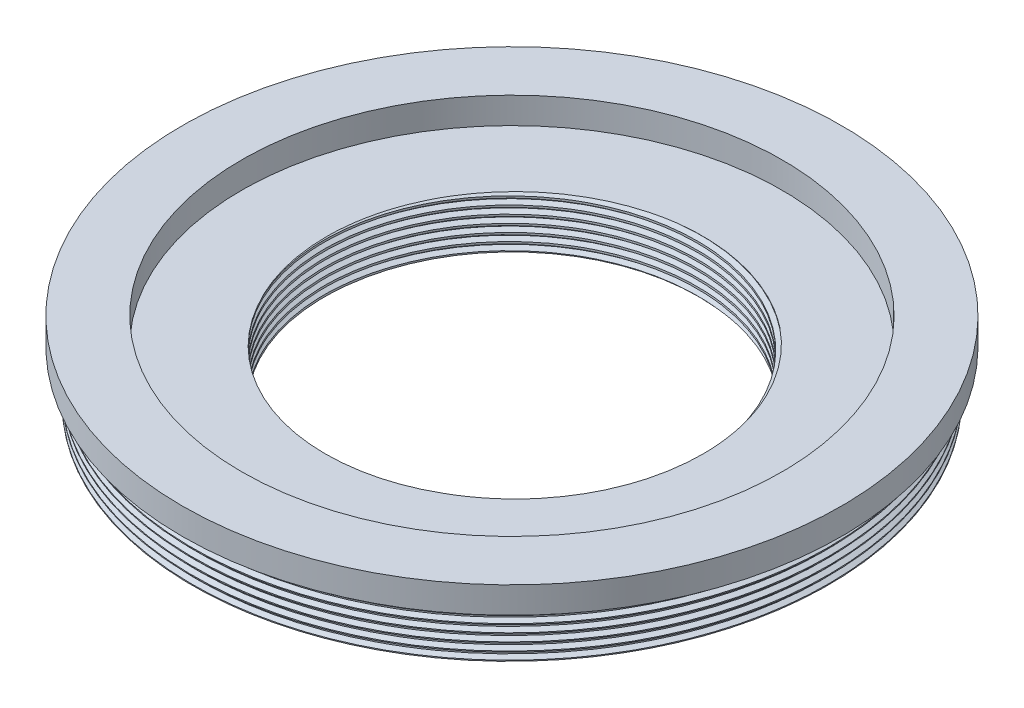
SolidWorks part; units mm, degrees
ref_plane "Front Plane" through (0, 0, 0) normal (0, 0, 1) x (1, 0, 0)
ref_plane "Top Plane" through (0, 0, 0) normal (0, 1, 0) x (1, 0, 0)
ref_plane "Right Plane" through (0, 0, 0) normal (1, 0, 0) x (0, 0, -1)
sketch "Sketch1" plane through (0, 0, 0) normal (0, 1, 0) x (1, 0, 0)
  circle A0 centre (0, 0) radius 23.8
  dimension "D1" = 47.6
extrude "Boss-Extrude1" add sketch "Sketch1" along normal blind 12.7
thread "MinColWidth_OnTracking1" pitch 0.6 method extrude profile "HeaderRowsCount1" start angle 0, offset 0, length 12.7, pitch 0.6, diameter 47.6
ref_plane "Plane1" through (-23.8, 12.7, 0) normal (0, 0, 1) x (-1, 0, 0)
sketch "HeaderRowsCount1" plane through (-23.8, 12.7, 0) normal (0, 0, 1) x (-1, 0, 0)
  line L0 (0, 0) -> (0, 0.6) construction
  line L1 (0, 0) -> (0.3248, 0.1875)
  line L2 (0.3248, 0.1875) -> (0.3248, 0.2625)
  line L3 (0.3248, 0.2625) -> (0, 0.45)
  line L4 (0.3248, 0.225) -> (0, 0.225) construction
  line L11 (0, 0) -> (0, 0.45)
  point P2 (0, 0)
  dimension "Pitch" = 0.6
  dimension "Profile_Angle" = 60
  dimension "Profile_Land" = 0.075
  dimension "Profile_Height" = 0.3248
sketch "Sketch2" plane through (0, 0, 0) normal (0, 0, 1) x (1, 0, 0)
  line L0 (0, 0) -> (0, 19.0669) construction
  line L1 (-25, 7.905) -> (25, 7.905)
  line L2 (-25, 7.905) -> (-25, 4.095)
  line L3 (-25, 4.095) -> (25, 4.095)
  line L4 (25, 7.905) -> (25, 4.095)
  line L5 (-25, 7.905) -> (25, 4.095) construction
  line L6 (-25, 4.095) -> (25, 7.905) construction
  point P0 (0, 6)
  dimension "D1" = 50
  dimension "D2" = 3.81
  dimension "D3" = 6
extrude "Cut-Extrude2" cut sketch "Sketch2" against normal through all both and the other way through all flip side to cut
sketch "Sketch3" plane through (0, 7.905, 0) normal (0, 1, 0) x (1, 0, 0)
  circle A0 centre (0, 0) radius 25
  dimension "D1" = 50
extrude "Boss-Extrude2" add sketch "Sketch3" along normal blind 2
sketch "Sketch4" plane through (0, 9.905, 0) normal (0, 1, 0) x (1, 0, 0)
  circle A0 centre (0, 0) radius 20.5
  dimension "D1" = 41
extrude "Cut-Extrude3" cut sketch "Sketch4" against normal up to surface (2 mm away) up to face at (0, 7.905, 25)
sketch "Sketch5" plane through (0, 7.905, 0) normal (0, 1, 0) x (1, 0, 0)
  circle A0 centre (0, 0) radius 14.15
  dimension "D1" = 28.3
extrude "Cut-Extrude4" cut sketch "Sketch5" against normal through all
thread "Thread1" pitch 0.6 method cut profile "Thread Profile1" start angle 0, offset 4, length 10, pitch 0.6, diameter 28.3
ref_plane "Plane2" through (-14.15, 11.905, 0) normal (0, 0, 1) x (-1, 0, 0)
sketch "Thread Profile1" plane through (-14.15, 11.905, 0) normal (0, 0, 1) x (-1, 0, 0)
  line L0 (0, 0) -> (0, 0.6) construction
  line L1 (0, 0) -> (0.3248, 0.1875)
  line L2 (0.3248, 0.1875) -> (0.3248, 0.2625)
  line L3 (0.3248, 0.2625) -> (0, 0.45)
  line L4 (0.3248, 0.225) -> (0, 0.225) construction
  line L11 (0, 0) -> (0, 0.45)
  point P2 (0, 0)
  dimension "Pitch" = 0.6
  dimension "Profile_Angle" = 60
  dimension "Profile_Land" = 0.075
  dimension "Profile_Height" = 0.3248
